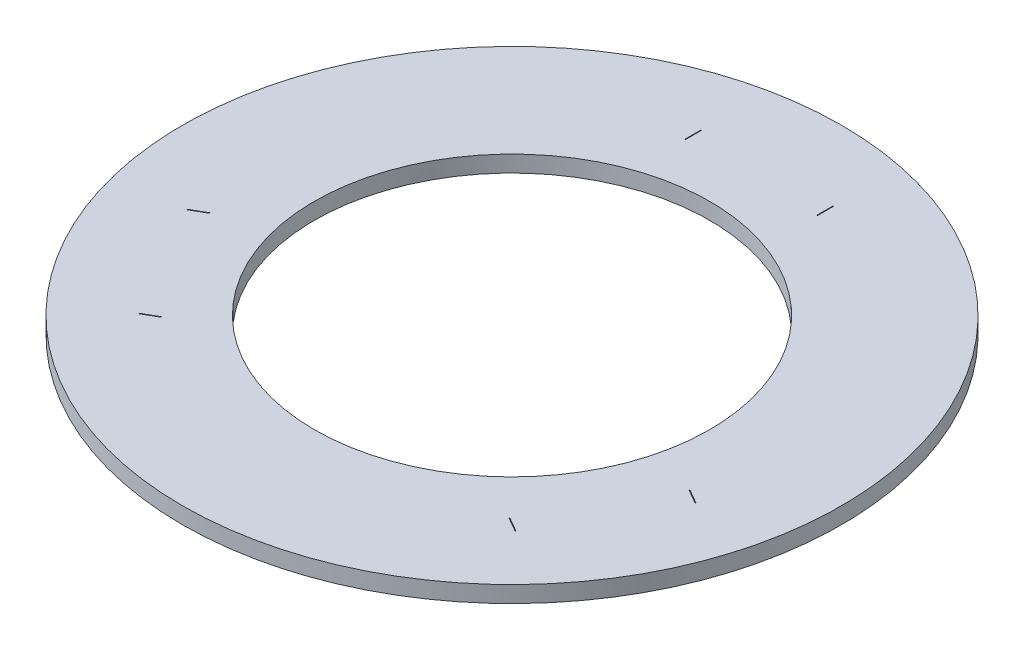
SolidWorks part; units mm, degrees
ref_plane "Front Plane" through (0, 0, 0) normal (0, 0, 1) x (1, 0, 0)
ref_plane "Top Plane" through (0, 0, 0) normal (0, 1, 0) x (1, 0, 0)
ref_plane "Right Plane" through (0, 0, 0) normal (1, 0, 0) x (0, 0, -1)
sketch "Sketch2" plane through (0, 0, 0) normal (0, 1, 0) x (1, 0, 0)
  circle A0 centre (0, 0) radius 100
  dimension "D1" = 200
extrude "Boss-Extrude1" add sketch "Sketch2" along normal blind 5
sketch "Sketch3" plane through (0, 5, 0) normal (0, 1, 0) x (1, 0, 0)
  line L0 (0, 0) -> (0, 100) construction
  line L1 (-20, 75) -> (20, 75) construction
  line L2 (72.8368, -18.8429) -> (77.167, -21.3429)
  line L3 (-20.1, 72.5) -> (-19.9, 72.5)
  line L4 (-20.1, 72.5) -> (-20.1, 77.5)
  line L5 (-20.1, 77.5) -> (-19.9, 77.5)
  line L6 (-19.9, 72.5) -> (-19.9, 77.5)
  line L7 (-20.1, 72.5) -> (-19.9, 77.5) construction
  line L8 (-20.1, 77.5) -> (-19.9, 72.5) construction
  line L9 (19.9, 72.5) -> (20.1, 72.5)
  line L10 (19.9, 72.5) -> (19.9, 77.5)
  line L11 (19.9, 77.5) -> (20.1, 77.5)
  line L12 (20.1, 72.5) -> (20.1, 77.5)
  line L13 (19.9, 72.5) -> (20.1, 77.5) construction
  line L14 (19.9, 77.5) -> (20.1, 72.5) construction
  line L15 (72.8368, -18.8429) -> (72.7368, -19.0161)
  line L16 (72.7368, -19.0161) -> (77.067, -21.5161)
  line L17 (77.167, -21.3429) -> (77.067, -21.5161)
  line L18 (52.8368, -53.4839) -> (57.167, -55.9839)
  line L19 (52.8368, -53.4839) -> (52.7368, -53.6571)
  line L20 (52.7368, -53.6571) -> (57.067, -56.1571)
  line L21 (57.167, -55.9839) -> (57.067, -56.1571)
  line L22 (-52.7368, -53.6571) -> (-57.067, -56.1571)
  line L23 (-52.7368, -53.6571) -> (-52.8368, -53.4839)
  line L24 (-52.8368, -53.4839) -> (-57.167, -55.9839)
  line L25 (-57.067, -56.1571) -> (-57.167, -55.9839)
  line L26 (-72.7368, -19.0161) -> (-77.067, -21.5161)
  line L27 (-72.7368, -19.0161) -> (-72.8368, -18.8429)
  line L28 (-72.8368, -18.8429) -> (-77.167, -21.3429)
  line L29 (-77.067, -21.5161) -> (-77.167, -21.3429)
  line L30 (0, 0) -> (-86.6025, -50) construction
  line L31 (-74.9019, -20.2661) -> (-55.0019, -54.7339) construction
  line L32 (0, 0) -> (86.6025, -50) construction
  line L33 (74.9019, -20.2661) -> (55.0019, -54.7339) construction
  circle A0 centre (0, 0) radius 100 construction
  point P8 (0, 75)
  point P36 (0, 0)
  dimension "D1" = 40
  dimension "D2" = 5
  dimension "D3" = 0.2
  dimension "D4" = 75
  dimension "D6" = 120
  dimension "D7" = 120
  dimension "D5" = 3
extrude "Cut-Extrude1" cut sketch "Sketch3" against normal through all
sketch "Sketch4" plane through (0, 5, 0) normal (0, 1, 0) x (1, 0, 0)
  circle A0 centre (0, 0) radius 60
  dimension "D1" = 120
extrude "Cut-Extrude2" cut sketch "Sketch4" against normal through all
equation "\"Leg_Spacing\"=40"
equation "\"D1@Sketch3\"=\"Leg_Spacing\""
equation "\"Leaf_Spring_Slot_Width\"=5"
equation "\"D2@Sketch3\"=\"Leaf_Spring_Slot_Width\""
equation "\"Leaf_Spring_Thickness\"=0.2"
equation "\"D3@Sketch3\"=\"Leaf_Spring_Thickness\""
equation "\"Inner_Radius\"=75"
equation "\"D4@Sketch3\"=\"Inner_Radius\""
equation "\"Camera\"=120"
equation "\"D1@Sketch4\"=\"Camera\""
